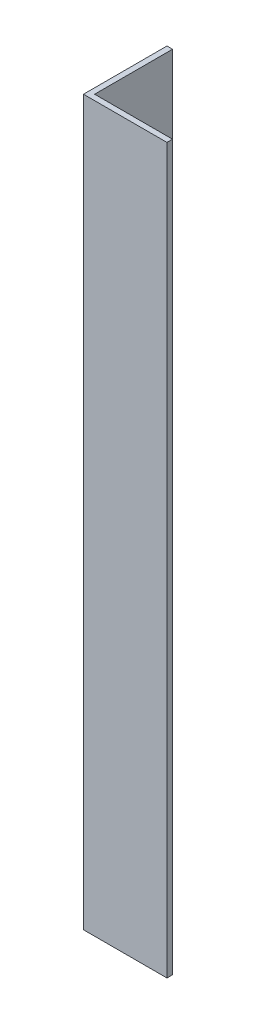
SolidWorks part; units mm, degrees
ref_plane "正面" through (0, 0, 0) normal (0, 0, 1) x (1, 0, 0)
ref_plane "平面" through (0, 0, 0) normal (0, 1, 0) x (1, 0, 0)
ref_plane "右側面" through (0, 0, 0) normal (1, 0, 0) x (0, 0, -1)
sketch "ｽｹｯﾁ1" plane through (0, 0, 0) normal (0, 1, 0) x (1, 0, 0)
  line L1 (0, 0) -> (15, 0)
  line L2 (0, 0) -> (0, -1)
  line L3 (0, -1) -> (15, -1)
  line L4 (15, 0) -> (15, -1)
  dimension "D1" = 15
  dimension "D2" = 1
sketch "ｽｹｯﾁ2" plane through (0, 0, 0) normal (0, 1, 0) x (1, 0, 0)
extrude "ﾎﾞｽ - 押し出し1" add sketch "ｽｹｯﾁ1" along normal blind 130
sketch "ｽｹｯﾁ3" plane through (0, 0, 0) normal (0, 0, -1) x (-1, 0, 0)
  line L1 (0, 130) -> (-1, 130)
  line L2 (0, 130) -> (0, 0)
  line L3 (0, 0) -> (-1, 0)
  line L4 (-1, 130) -> (-1, 0)
  dimension "D1" = 1
  dimension "D2" = 130
extrude "ﾎﾞｽ - 押し出し2" add sketch "ｽｹｯﾁ3" along normal blind 14
hole_wizard "M3x0.5 ねじ穴1" positions "ｽｹｯﾁ4" profile "ｽｹｯﾁ5" tap size "M3x0.5" standard "JIS" end condition through all
sketch "ｽｹｯﾁ4" plane through (0, 0, 0) normal (-1, 0, 0) x (0, 0, 1)
  line L0 (6.6, 0) -> (-6.6, 0) construction
  line L1 (-14, 0) -> (-14, 130) construction
  point P0 (-7, 15)
  point P2 (-7, 75)
  dimension "D1" = 15
  dimension "D2" = 60
  dimension "D3" = 7
  dimension "D4" = 7
sketch "ｽｹｯﾁ5" plane through (0, 15, -7) normal (0, 1, 0) x (0, 0, 1)
  line L0 (0, 0) -> (0, 15)
  line L1 (0, 15) -> (1.25, 15)
  line L2 (1.25, 15) -> (1.25, 0)
  line L5 (1.25, 0) -> (0, 0)
  line L11 (0, -6.35) -> (0, 107.95) construction
  dimension "次ｻｰﾌｪｽまでのねじ下穴ﾄﾞﾘﾙ直径" = 2.5
  dimension "次ｻｰﾌｪｽまでのねじ下穴ﾄﾞﾘﾙの深さ" = 15
cosmetic thread "穴のねじ山1" parameters "D2"=3
cosmetic thread "穴のねじ山2" parameters "D2"=3
